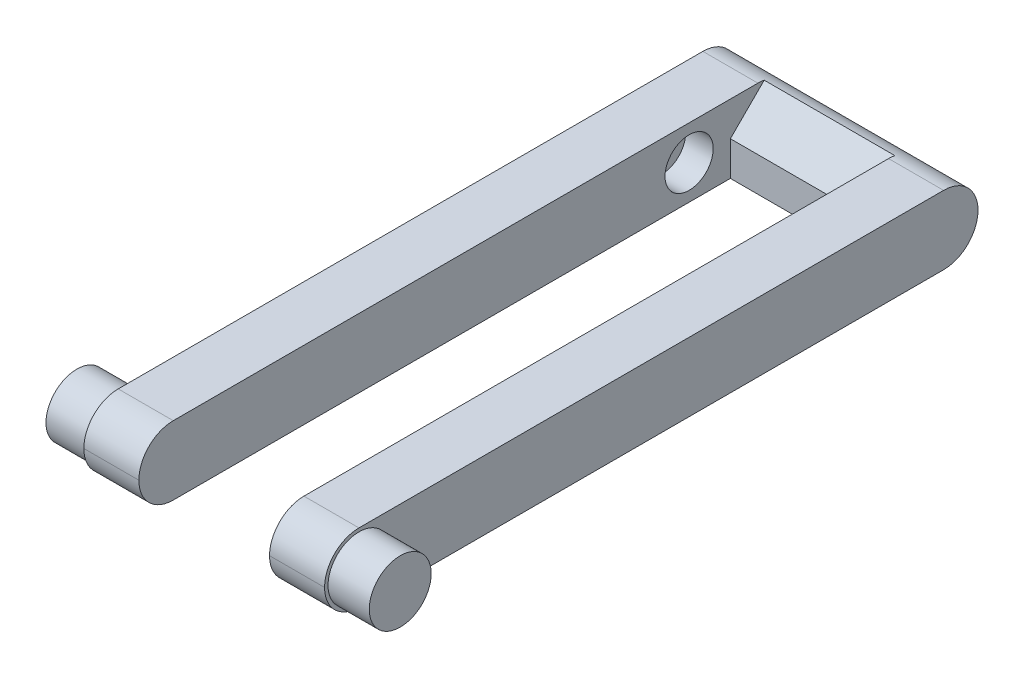
SolidWorks part; units mm, degrees
ref_plane "Front Plane" through (0, 0, 0) normal (0, 0, 1) x (1, 0, 0)
ref_plane "Top Plane" through (0, 0, 0) normal (0, 1, 0) x (1, 0, 0)
ref_plane "Right Plane" through (0, 0, 0) normal (1, 0, 0) x (0, 0, -1)
sketch "Sketch1" plane through (0, 0, 0) normal (0, 1, 0) x (1, 0, 0)
  line L1 (0, 0) -> (17.5, 0)
  line L2 (0, 0) -> (0, -47.5)
  line L3 (0, -47.5) -> (17.5, -47.5)
  line L4 (17.5, 0) -> (17.5, -47.5)
  line L5 (4, -47.5) -> (13.5, -47.5)
  line L6 (4, -47.5) -> (4, -4.5)
  line L7 (4, -4.5) -> (13.5, -4.5)
  line L8 (13.5, -47.5) -> (13.5, -4.5)
  dimension "D1" = 17.5
  dimension "D2" = 47.5
  dimension "D3" = 4
  dimension "D4" = 4
  dimension "D5" = 4.5
extrude "Boss-Extrude1" add sketch "Sketch1" along normal blind 5 contours L8 L3 L4 L1 L2 L6 L7 region at (8.75, 0, 0.5062)
sketch "Sketch2" plane through (17.5, 0, 0) normal (1, 0, 0) x (0, 0, -1)
  line L0 (-47.5, 5) -> (-47.5, 0) construction
  line L1 (0, 5) -> (-47.5, 5) construction
  circle A0 centre (-45, 2.5) radius 2.25
  point P4 (-47.5, 2.5)
  dimension "D1" = 2.5
  dimension "D2" = 2.5
  dimension "D3" = 4.5
extrude "Boss-Extrude2" add sketch "Sketch2" along normal blind 3
fillet "Fillet3" radius 2.5 2 edges at (15.5, 0, 47.5) (15.5, 5, 47.5)
sketch "Sketch3" plane through (0, 0, 0) normal (-1, 0, 0) x (0, 0, 1)
  line L0 (47.5, 5) -> (47.5, 0) construction
  line L1 (0, 5) -> (47.5, 5) construction
  circle A0 centre (45, 2.5) radius 2.25
  dimension "D1" = 2.5
  dimension "D2" = 2.5
  dimension "D3" = 4.5
extrude "Boss-Extrude3" add sketch "Sketch3" along normal blind 3
fillet "Fillet4" radius 2.5 2 edges at (2, 0, 47.5) (2, 5, 47.5)
fillet "Chamfer1" radius 2.5 1 edges at (8.75, 5, 4.5) type face fillet profile chamfer first side face at (8.75, 5, 23.625) second side face at (8.75, 2.5, 4.5)
fillet "Fillet5" radius 2.5 2 edges at (8.75, 0, 0) (8.75, 5, 0)
sketch "Sketch4" plane through (13.5, 0, 0) normal (-1, 0, 0) x (0, 0, 1)
  line L0 (45, 5) -> (2.5, 5) construction
  line L1 (4.5, 2.5) -> (4.5, 0) construction
  circle A0 centre (7.5, 2.5) radius 1.75
  dimension "D1" = 2.5
  dimension "D2" = 3
  dimension "D3" = 3.5
extrude "Cut-Extrude1" cut sketch "Sketch4" against normal blind 2 and the other way blind 11.5
